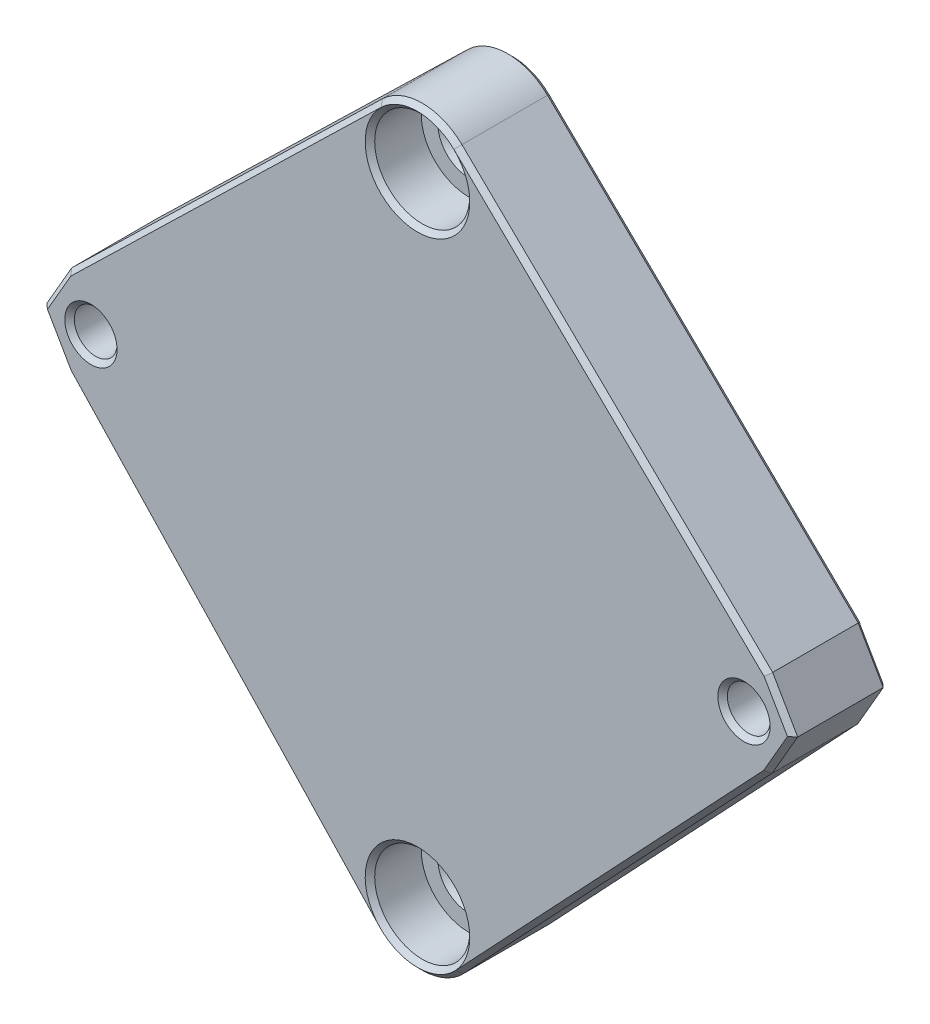
SolidWorks part; units mm, degrees
ref_plane "Top" through (0, 0, 0) normal (0, 0, 1) x (1, 0, 0)
ref_plane "Front" through (0, 0, 0) normal (0, 1, 0) x (1, 0, 0)
ref_plane "Right" through (0, 0, 0) normal (1, 0, 0) x (0, 0, -1)
sketch "Sketch1" plane through (0, 0, 0) normal (0, 0, 1) x (1, 0, 0)
  line L1 (0, 0) -> (79, 0)
  line L2 (0, 0) -> (0, 87)
  line L3 (0, 87) -> (79, 87)
  line L4 (79, 0) -> (79, 87)
  dimension "D1" = 79
  dimension "D2" = 87
extrude "Boss-Extrude1" add sketch "Sketch1" along normal blind 10
sketch "Sketch4" plane through (0, 0, 10) normal (0, 0, 1) x (1, 0, 0)
  line L0 (5.15, 45) -> (73.85, 45)
  line L2 (79, 0) -> (79, 87) construction
  line L5 (79, 87) -> (0, 87) construction
  point P2 (39.5, 45)
  dimension "D1" = 68.7
  dimension "D2" = 39.5
  dimension "D3" = 42
hole_wizard "M4 Clearance Hole1" positions "Sketch5" profile "Sketch6" hole size "M4" standard "DIN" end condition through all
sketch "Sketch5" plane through (0, 0, 10) normal (0, 0, 1) x (1, 0, 0)
  point P0 (5.15, 45)
  point P3 (73.85, 45)
sketch "Sketch6" plane through (5.15, 45, 10) normal (1, 0, 0) x (0, -1, 0)
  line L0 (0, 0) -> (0, 10)
  line L1 (0, 10) -> (2.25, 10)
  line L2 (2.25, 10) -> (2.25, 0)
  line L5 (2.25, 0) -> (0, 0)
  line L11 (0, -6.35) -> (0, 107.95) construction
  dimension "Thru Hole Dia." = 4.5
  dimension "Thru Hole Depth" = 10
sketch "Sketch11" plane through (0, 0, 0) normal (0, 0, -1) x (-1, 0, 0)
  line L0 (-79, 87) -> (0, 87) construction
  line L1 (-69.6353, 45) -> (-71.7427, 48.65)
  line L2 (-71.7427, 48.65) -> (-75.9573, 48.65)
  line L3 (-75.9573, 48.65) -> (-78.0647, 45)
  line L4 (-78.0647, 45) -> (-75.9573, 41.35)
  line L5 (-75.9573, 41.35) -> (-71.7427, 41.35)
  line L6 (-71.7427, 41.35) -> (-69.6353, 45)
  line L7 (-9.3647, 45) -> (-7.2573, 41.35)
  line L8 (-7.2573, 41.35) -> (-3.0427, 41.35)
  line L9 (-3.0427, 41.35) -> (-0.9353, 45)
  line L10 (-0.9353, 45) -> (-3.0427, 48.65)
  line L11 (-3.0427, 48.65) -> (-7.2573, 48.65)
  line L12 (-7.2573, 48.65) -> (-9.3647, 45)
  circle A0 centre (-73.85, 45) radius 3.65 construction
  circle A1 centre (-5.15, 45) radius 3.65 construction
  dimension "D1" = 7.3
  dimension "D2" = 7.3
extrude "Cut-Extrude3" cut sketch "Sketch11" against normal blind 3.5
sketch "Sketch12" plane through (0, 0, 10) normal (0, 0, -1) x (-1, 0, 0)
  line L0 (-39.5, 77) -> (-39.5, 10)
  line L1 (-79, 0) -> (-79, 87) construction
  line L3 (-79, 87) -> (0, 87) construction
  dimension "D1" = 39.5
  dimension "D2" = 67
  dimension "D3" = 10
hole_wizard "CBORE for M5 Socket Head Cap Screw1" positions "Sketch15" profile "Sketch16" counterbore size "M5" standard "DIN" end condition through all
sketch "Sketch15" plane through (0, 0, 10) normal (0, 0, 1) x (1, 0, 0)
  point P0 (39.5, 77)
  point P3 (39.5, 10)
sketch "Sketch16" plane through (39.5, 77, 10) normal (1, 0, 0) x (0, -1, 0)
  line L0 (0, 0) -> (0, 10)
  line L1 (0, 10) -> (2.75, 10)
  line L3 (2.75, 10) -> (2.75, 5.4)
  line L4 (2.75, 5.4) -> (5, 5.4)
  line L5 (5, 5.4) -> (5, 0)
  line L7 (5, 0) -> (0, 0)
  line L11 (0, -6.35) -> (0, 107.95) construction
  dimension "Thru Hole Dia." = 5.5
  dimension "Thru Hole Depth" = 10
  dimension "C'Bore Dia." = 10
  dimension "C'Bore Depth" = 5.4
sketch "Sketch17" plane through (0, 0, 0) normal (0, 0, -1) x (-1, 0, 0)
  line L0 (-76.3644, 49.565) -> (-43.68, 81.3044)
  line L2 (-35.32, 81.3044) -> (-2.6356, 49.565)
  line L4 (-76.3286, 40.3729) -> (-43.869, 5.8876)
  line L5 (-35.131, 5.8876) -> (-2.6714, 40.3729)
  line L14 (-2.6714, 40.3729) -> (0, 45)
  line L15 (0, 87) -> (0, 0) construction
  line L16 (0, 45) -> (-2.6356, 49.565)
  line L17 (-0.9353, 45) -> (-3.0427, 48.65) construction
  line L18 (-3.0427, 41.35) -> (-0.9353, 45) construction
  line L20 (-76.3644, 49.565) -> (-79, 45)
  line L21 (-79, 0) -> (-79, 87) construction
  line L22 (-79, 45) -> (-76.3286, 40.3729)
  line L23 (-78.0647, 45) -> (-75.9573, 41.35) construction
  line L24 (-75.9573, 48.65) -> (-78.0647, 45) construction
  line L25 (-125.188, 45) -> (-108.6437, 16.3444)
  line L26 (-108.6437, 16.3444) -> (-72.9959, -21.5282)
  line L27 (-6.0041, -21.5282) -> (29.6437, 16.3444)
  line L28 (29.6437, 16.3444) -> (46.188, 45)
  line L29 (46.188, 45) -> (29.223, 74.3843)
  line L30 (-7.4537, 110.0005) -> (29.223, 74.3843)
  line L31 (-108.223, 74.3843) -> (-71.5463, 110.0005)
  line L32 (-108.223, 74.3843) -> (-125.188, 45)
  arc A0 (-43.68, 81.3044) -> (-35.32, 81.3044) centre (-39.5, 77) cw
  arc A1 (-43.869, 5.8876) -> (-35.131, 5.8876) centre (-39.5, 10) ccw
  arc A4 (-72.9959, -21.5282) -> (-6.0041, -21.5282) centre (-39.5, 10) ccw
  arc A5 (-71.5463, 110.0005) -> (-7.4537, 110.0005) centre (-39.5, 77) cw
  dimension "D2" = 6
  dimension "D4" = 6
  dimension "D1" = 0.94
  dimension "D3" = 0.94
  dimension "D5" = 0.94
  dimension "D6" = 0.94
  dimension "D7" = 40
extrude "Cut-Extrude4" cut sketch "Sketch17" against normal blind 10
chamfer "Chamfer1" distance 0.5 angle 45 38 edges at (77.6643, 42.6865, 10) (60.0988, 23.1303, 10) (39.5, 4, 10) (18.9012, 23.1303, 10) (1.3357, 42.6865, 10) (1.3178, 47.2825, 10) (18.9778, 65.4347, 10) (39.5, 83, 10) (60.0222, 65.4347, 10) (77.6822, 47.2825, 10) (76.1, 45, 10) (7.4, 45, 10) (44.5, 10, 10) (44.5, 77, 10) (39.5, 83, 0) (18.9778, 65.4347, 0) (1.3178, 47.2825, 0) (1.3357, 42.6865, 0) (18.9012, 23.1303, 0) (39.5, 4, 0) (60.0988, 23.1303, 0) (77.6643, 42.6865, 0) (77.6822, 47.2825, 0) (60.0222, 65.4347, 0) (8.311, 43.175, 0) (5.15, 41.35, 0) (1.989, 43.175, 0) (1.989, 46.825, 0) (5.15, 48.65, 0) (8.311, 46.825, 0) (70.689, 46.825, 0) (73.85, 48.65, 0) (77.011, 46.825, 0) (77.011, 43.175, 0) (73.85, 41.35, 0) (70.689, 43.175, 0) (42.25, 10, 0) (42.25, 77, 0)
chamfer "Chamfer2" distance 0.5 angle 45 2 edges at (42.25, 10, 4.6) (42.25, 77, 4.6)
